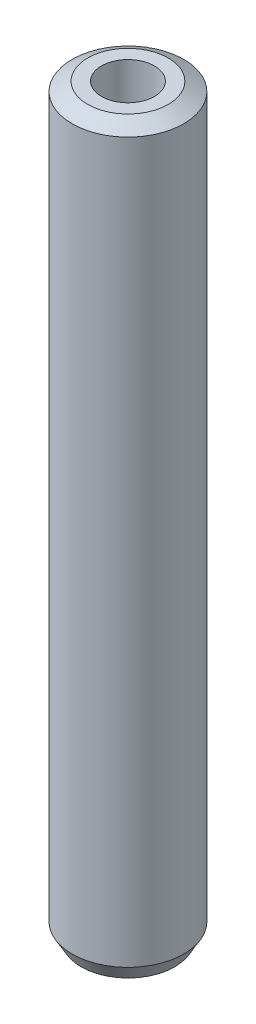
SolidWorks part; units mm, degrees
ref_plane "Front Plane" through (0, 0, 0) normal (0, 0, 1) x (1, 0, 0)
ref_plane "Top Plane" through (0, 0, 0) normal (0, 1, 0) x (1, 0, 0)
ref_plane "Right Plane" through (0, 0, 0) normal (1, 0, 0) x (0, 0, -1)
sketch "Sketch1" plane through (0, 0, 0) normal (0, 1, 0) x (1, 0, 0)
  circle A0 centre (0, 0) radius 20
  dimension "SHAFT_OD" = 40
extrude "Boss-Extrude1" add sketch "Sketch1" along normal blind 266.4596
sketch "Sketch2" plane through (0, 0, 0) normal (0, 1, 0) x (1, 0, 0)
  circle A0 centre (0, 0) radius 9.4915
  dimension "BORE_D" = 18.9829
extrude "Cut-Extrude1" cut sketch "Sketch2" along normal through all
chamfer "Chamfer1" distance 3.2225 angle 60 2 edges at (0, 266.4596, 20) (0, 0, 20) first distance on face at (0, 266.4596, 20) first distance on face at (0, 0, 9.4915)
